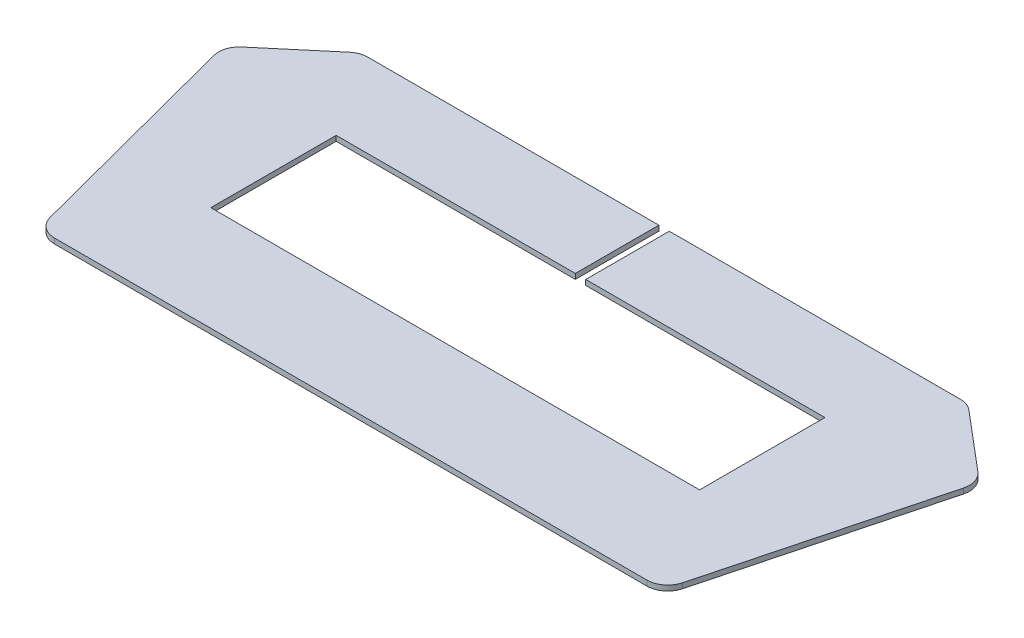
SolidWorks part; units mm, degrees
note: The reader was unsure of these and kept them because the rebuilt part matched: thickness of "Base-Flange1", "Sheet-Metal2".
ref_plane "Front Plane" through (0, 0, 0) normal (0, 0, 1) x (1, 0, 0)
ref_plane "Top Plane" through (0, 0, 0) normal (0, 1, 0) x (1, 0, 0)
ref_plane "Right Plane" through (0, 0, 0) normal (1, 0, 0) x (0, 0, -1)
sketch "Sketch1" plane through (0, 0, 0) normal (0, 1, 0) x (1, 0, 0)
  line L0 (0, 0) -> (0, -6864.9507) construction
  line L1 (0, 0) -> (6864.9507, 0) construction
  line L2 (-14.1786, -8) -> (14.1786, -8)
  line L3 (-11.7, 3) -> (-0.25, 3)
  line L4 (-11.7, 3) -> (-11.7, -3)
  line L5 (-11.7, -3) -> (11.7, -3)
  line L6 (11.7, 3) -> (11.7, -3)
  line L7 (-14.1841, 7) -> (-0.25, 7)
  line L8 (-15.1459, -7.2539) -> (-17.9398, 3.3896)
  line L9 (-17.618, 4.4073) -> (-14.8295, 6.7638)
  line L10 (15.1459, -7.2539) -> (17.9398, 3.3896)
  line L11 (17.618, 4.4073) -> (14.8295, 6.7638)
  line L12 (-0.25, 7) -> (-0.25, 3)
  line L13 (0.25, 7) -> (0.25, 3)
  line L14 (0.25, 7) -> (14.1841, 7)
  line L15 (0.25, 3) -> (11.7, 3)
  arc A0 (-14.1786, -8) -> (-15.1459, -7.2539) centre (-14.1786, -7) cw
  arc A1 (-17.9398, 3.3896) -> (-17.618, 4.4073) centre (-16.9725, 3.6435) cw
  arc A2 (-14.8295, 6.7638) -> (-14.1841, 7) centre (-14.1841, 6) cw
  arc A3 (14.1841, 7) -> (14.8295, 6.7638) centre (14.1841, 6) cw
  arc A4 (17.618, 4.4073) -> (17.9398, 3.3896) centre (16.9725, 3.6435) cw
  arc A5 (14.1786, -8) -> (15.1459, -7.2539) centre (14.1786, -7) ccw
  circle A6 centre (-14.2, -7) radius 0.5
  circle A7 centre (14.2, -7) radius 0.5
  circle A8 centre (-16.6, 3.6435) radius 0.5
  circle A9 centre (16.6, 3.6435) radius 0.5
  circle A10 centre (-11.85, 5) radius 0.5
  circle A11 centre (11.85, 5) radius 0.5
  point P18 (-14.95, -8)
  point P21 (-18.1, 4)
  point P24 (-14.55, 7)
  point P27 (14.55, 7)
  point P30 (18.1, 4)
  point P33 (14.95, -8)
  dimension "D8" = 1
  dimension "D9" = 1
  dimension "D10" = 1
  dimension "D11" = 1
  dimension "D12" = 1
  dimension "D13" = 1
  dimension "D14" = 1
  dimension "D15" = 1
  dimension "D18" = 2.5
  dimension "D20" = 1
  dimension "D21" = 1
  dimension "D24" = 1
  dimension "D1" = 6
  dimension "D2" = 5
  dimension "D3" = 4
  dimension "D4" = 29.1
  dimension "D5" = 29.9
  dimension "D6" = 36.2
  dimension "D7" = 12
  dimension "D16" = 28.4
  dimension "D17" = 1
  dimension "D19" = 1.5
  dimension "D22" = 3.3565
  dimension "D23" = 4.75
  dimension "D25" = 13
  dimension "D26" = 0.5
base flange "Base-Flange1" sketch "Sketch1" thickness 0.25 reverse thickness direction no parameters "D1"=0.7366
sketch "Orientation Sketch" plane through (0, 0, 0) normal (0, 1, 0) x (1, 0, 0)
  line L0 (-11.7, -3) -> (-11.7, 3) construction
  line L1 (-11.7, 3) -> (-0.25, 3) construction
  line L2 (-0.25, 3) -> (-0.25, 7) construction
  line L3 (-0.25, 7) -> (-14.1841, 7) construction
  line L4 (-14.8295, 6.7638) -> (-17.618, 4.4073) construction
  line L5 (-17.9398, 3.3896) -> (-15.1459, -7.2539) construction
  line L6 (-14.1786, -8) -> (14.1786, -8) construction
  line L7 (15.1459, -7.2539) -> (17.9398, 3.3896) construction
  line L8 (17.618, 4.4073) -> (14.8295, 6.7638) construction
  line L9 (14.1841, 7) -> (0.25, 7) construction
  line L10 (0.25, 7) -> (0.25, 3) construction
  line L11 (0.25, 3) -> (11.7, 3) construction
  line L12 (11.7, 3) -> (11.7, -3) construction
  line L13 (11.7, -3) -> (-11.7, -3) construction
  line L14 (-11.7, -3) -> (-11.7, 3) construction
  line L15 (-11.7, 3) -> (-0.25, 3) construction
  line L16 (-0.25, 3) -> (-0.25, 7) construction
  line L17 (-0.25, 7) -> (-14.1841, 7) construction
  line L18 (-14.8295, 6.7638) -> (-17.618, 4.4073) construction
  line L19 (-17.9398, 3.3896) -> (-15.1459, -7.2539) construction
  line L20 (-14.1786, -8) -> (14.1786, -8) construction
  line L21 (15.1459, -7.2539) -> (17.9398, 3.3896) construction
  line L22 (17.618, 4.4073) -> (14.8295, 6.7638) construction
  line L23 (14.1841, 7) -> (0.25, 7) construction
  line L24 (0.25, 7) -> (0.25, 3) construction
  line L25 (0.25, 3) -> (11.7, 3) construction
  line L26 (11.7, 3) -> (11.7, -3) construction
  line L27 (11.7, -3) -> (-11.7, -3) construction
  circle A0 centre (-11.85, 5) radius 0.5 construction
  circle A1 centre (11.85, 5) radius 0.5 construction
  circle A2 centre (16.6, 3.6435) radius 0.5 construction
  circle A3 centre (-16.6, 3.6435) radius 0.5 construction
  circle A4 centre (14.2, -7) radius 0.5 construction
  circle A5 centre (-14.2, -7) radius 0.5 construction
  arc A6 (-14.1841, 7) -> (-14.8295, 6.7638) centre (-14.1841, 6) ccw construction
  arc A7 (-17.618, 4.4073) -> (-17.9398, 3.3896) centre (-16.9725, 3.6435) ccw construction
  arc A8 (-15.1459, -7.2539) -> (-14.1786, -8) centre (-14.1786, -7) ccw construction
  arc A9 (14.1786, -8) -> (15.1459, -7.2539) centre (14.1786, -7) ccw construction
  arc A10 (17.9398, 3.3896) -> (17.618, 4.4073) centre (16.9725, 3.6435) ccw construction
  arc A11 (14.8295, 6.7638) -> (14.1841, 7) centre (14.1841, 6) ccw construction
  circle A12 centre (-11.85, 5) radius 0.5
  circle A13 centre (11.85, 5) radius 0.5
  circle A14 centre (16.6, 3.6435) radius 0.5
  circle A15 centre (-16.6, 3.6435) radius 0.5
  circle A16 centre (14.2, -7) radius 0.5
  circle A17 centre (-14.2, -7) radius 0.5
  arc A18 (-14.1841, 7) -> (-14.8295, 6.7638) centre (-14.1841, 6) ccw construction
  arc A19 (-17.618, 4.4073) -> (-17.9398, 3.3896) centre (-16.9725, 3.6435) ccw construction
  arc A20 (-15.1459, -7.2539) -> (-14.1786, -8) centre (-14.1786, -7) ccw construction
  arc A21 (14.1786, -8) -> (15.1459, -7.2539) centre (14.1786, -7) ccw construction
  arc A22 (17.9398, 3.3896) -> (17.618, 4.4073) centre (16.9725, 3.6435) ccw construction
  arc A23 (14.8295, 6.7638) -> (14.1841, 7) centre (14.1841, 6) ccw construction
  point P28 (0, -0.5)
other "FormTool1"
sketch "Bend-Lines1" [suppressed] plane through (0, 0, 0) normal (0, 1, 0) x (1, 0, 0)
sketch "Bounding-Box1" [suppressed] plane through (0, 0, 0) normal (0, 1, 0) x (1, 0, 0)
sheet metal parameters "Sheet-Metal2" thickness 0.25 parameters "D1"=0.7366
flat pattern "Flat-Pattern2" [suppressed]
sketch "Bend-Lines2" plane through (0, 0, 0) normal (0, 1, 0) x (1, 0, 0)
sketch3d "Bounding-Box2" [suppressed]
  line L0 (3.7876, 1, 0) -> (-32.1561, 1, 0) construction
  line L1 (3.7876, -14, 0) -> (-32.1561, -14, 0) construction
  line L2 (3.7876, 1, 0) -> (3.7876, -14, 0) construction
  line L3 (-32.1561, 1, 0) -> (-32.1561, -14, 0) construction
